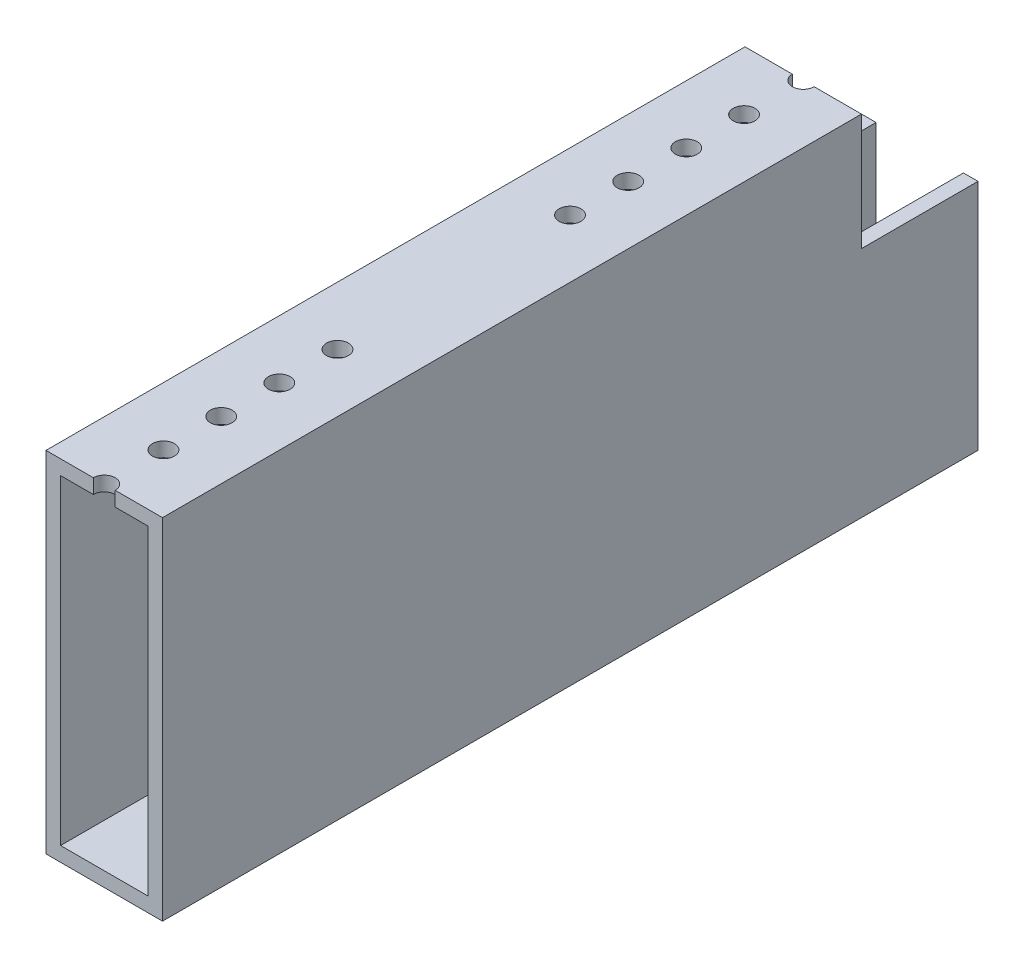
SolidWorks part; units mm, degrees
ref_plane "Front Plane" through (0, 0, 0) normal (0, 0, 1) x (1, 0, 0)
ref_plane "Top Plane" through (0, 0, 0) normal (0, 1, 0) x (1, 0, 0)
ref_plane "Right Plane" through (0, 0, 0) normal (1, 0, 0) x (0, 0, -1)
sketch "Sketch1" plane through (0, 0, 0) normal (0, 0, 1) x (1, 0, 0)
  line L1 (-12.7, -38.1) -> (12.7, -38.1)
  line L2 (-12.7, -38.1) -> (-12.7, 38.1)
  line L3 (-12.7, 38.1) -> (12.7, 38.1)
  line L4 (12.7, -38.1) -> (12.7, 38.1)
  line L5 (-12.7, -38.1) -> (12.7, 38.1) construction
  line L6 (-12.7, 38.1) -> (12.7, -38.1) construction
  point P0 (0, 0)
  dimension "D1" = 25.4
  dimension "D2" = 76.2
extrude "Boss-Extrude1" add sketch "Sketch1" along normal mid plane 177.8
shell "Shell1" thickness 3.175 removed face at (0, 0, -88.9) removed face at (0, 0, 88.9)
sketch "Sketch2" plane through (-12.7, 0, 0) normal (-1, 0, 0) x (0, 0, 1)
  line L1 (-88.9, 38.1) -> (-63.5, 38.1)
  line L2 (-88.9, 38.1) -> (-88.9, 12.7)
  line L3 (-88.9, 12.7) -> (-63.5, 12.7)
  line L4 (-63.5, 38.1) -> (-63.5, 12.7)
  dimension "D1" = 25.4
extrude "Cut-Extrude1" cut sketch "Sketch2" against normal through all
sketch "Sketch3" plane through (0, 38.1, 0) normal (0, 1, 0) x (1, 0, 0)
  line L0 (9.525, -88.9) -> (-9.525, -88.9) construction
  line L1 (12.7, -88.9) -> (-12.7, -88.9) construction
  line L2 (-12.7, -88.9) -> (-12.7, 63.5) construction
  line L3 (-20.8214, -12.7) -> (21.7075, -12.7) construction
  circle A0 centre (0, -88.9) radius 2.3812
  circle A1 centre (0, -75.9959) radius 2.3812
  circle A2 centre (0, -63.3973) radius 2.3812
  circle A3 centre (0, -50.7315) radius 2.3812
  circle A4 centre (0, -38.0486) radius 2.3812
  circle A5 centre (0, 63.5) radius 2.3812
  circle A6 centre (0, 12.6486) radius 2.3812
  circle A7 centre (0, 25.3315) radius 2.3812
  circle A8 centre (0, 37.9973) radius 2.3812
  circle A9 centre (0, 50.5959) radius 2.3812
  point P10 (0, -88.9)
  point P15 (-12.7, -12.7)
  dimension "D1" = 4.7625
  dimension "D3" = 12.9041
  dimension "D2" = 0
  dimension "D4" = 25.5027
  dimension "D5" = 38.1685
  dimension "D6" = 50.8514
extrude "Cut-Extrude2" cut sketch "Sketch3" against normal up to next
sketch "Sketch4" plane through (0, 38.1, 0) normal (0, 1, 0) x (1, 0, 0)
  line L2 (-12.7, -88.9) -> (-12.7, -12.7)
  line L3 (-12.7, -88.9) -> (-12.7, 63.5) construction
  line L4 (-20.5201, -12.7) -> (22.1381, -12.7) construction
